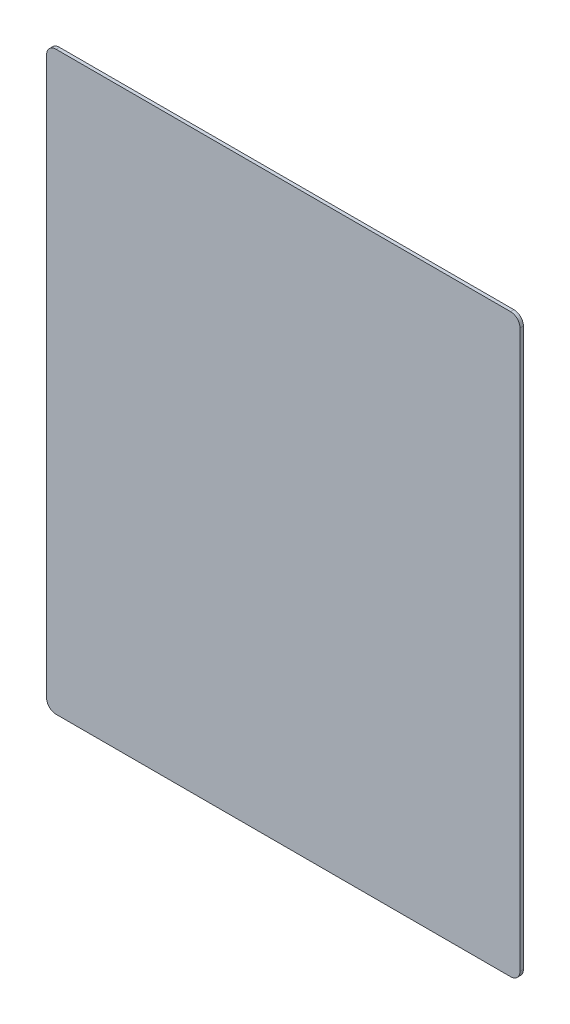
SolidWorks part; units mm, degrees
ref_plane "前视基准面" through (0, 0, 0) normal (0, 0, 1) x (1, 0, 0)
ref_plane "上视基准面" through (0, 0, 0) normal (0, 1, 0) x (1, 0, 0)
ref_plane "右视基准面" through (0, 0, 0) normal (1, 0, 0) x (0, 0, -1)
other "Configuration Table"
sketch "草图1" plane through (0, 0, 0) normal (0, 0, 1) x (1, 0, 0)
  line L1 (-38.1507, 36.488) -> (31.9593, 36.488)
  line L2 (-38.1507, 36.488) -> (-38.1507, -48.812)
  line L3 (-38.1507, -48.812) -> (31.9593, -48.812)
  line L4 (31.9593, 36.488) -> (31.9593, -48.812)
  line L5 (-37.1507, 34.488) -> (30.9593, 34.488)
  line L6 (-37.1507, 34.488) -> (-37.1507, -46.812)
  line L7 (-37.1507, -46.812) -> (30.9593, -46.812)
  line L8 (30.9593, 34.488) -> (30.9593, -46.812)
  line L9 (-36.7197, 34.058) -> (30.5283, 34.058)
  line L10 (-36.7197, 34.058) -> (-36.7197, -46.382)
  line L11 (-36.7197, -46.382) -> (30.5283, -46.382)
  line L12 (30.5283, 34.058) -> (30.5283, -46.382)
  line L13 (-18.6417, 14.688) -> (-5.6417, 14.688)
  line L14 (-18.6417, 14.688) -> (-18.6417, 10.188)
  line L15 (-18.6417, 10.188) -> (-5.6417, 10.188)
  line L16 (-5.6417, 14.688) -> (-5.6417, 10.188)
  point P12 (-3.0957, 34.488)
  point P13 (-3.0957, 34.058)
  point P18 (-12.1417, 14.688)
  dimension "D1" = 70.11
  dimension "D2" = 85.3
  dimension "D3" = 1
  dimension "D4" = 1
  dimension "D5" = 2
  dimension "D6" = 2
  dimension "D7" = 67.248
  dimension "D8" = 13
  dimension "D9" = 4.5
  dimension "D10" = 42.67
  dimension "D11" = 26.3
  dimension "D12" = 0.43
  dimension "D13" = 0.43
extrude "凸台-拉伸1" add sketch "草图1" along normal blind 0.5 contours L1 L4 L3 L2
extrude "凸台-拉伸2" add sketch "草图1<3>" against normal blind 0.7 contours L5 L8 L7 L6
sketch "草图1<3>" plane through (0, 0, 0) normal (0, 0, 1) x (1, 0, 0) same geometry as "草图1"
fillet "圆角1" radius 1.4 4 edges at (30.9593, -46.812, -0.35) (-37.1507, -46.812, -0.35) (30.9593, 34.488, -0.35) (-37.1507, 34.488, -0.35)
fillet "圆角2" radius 1.4 4 edges at (-38.1507, -48.812, 0.25) (31.9593, -48.812, 0.25) (31.9593, 36.488, 0.25) (-38.1507, 36.488, 0.25)
extrude "凸台-拉伸3" add sketch "草图1<4>" against normal blind 1 contours L13 L16 L15 L14
sketch "草图1<4>" plane through (0, 0, 0) normal (0, 0, 1) x (1, 0, 0) same geometry as "草图1"
